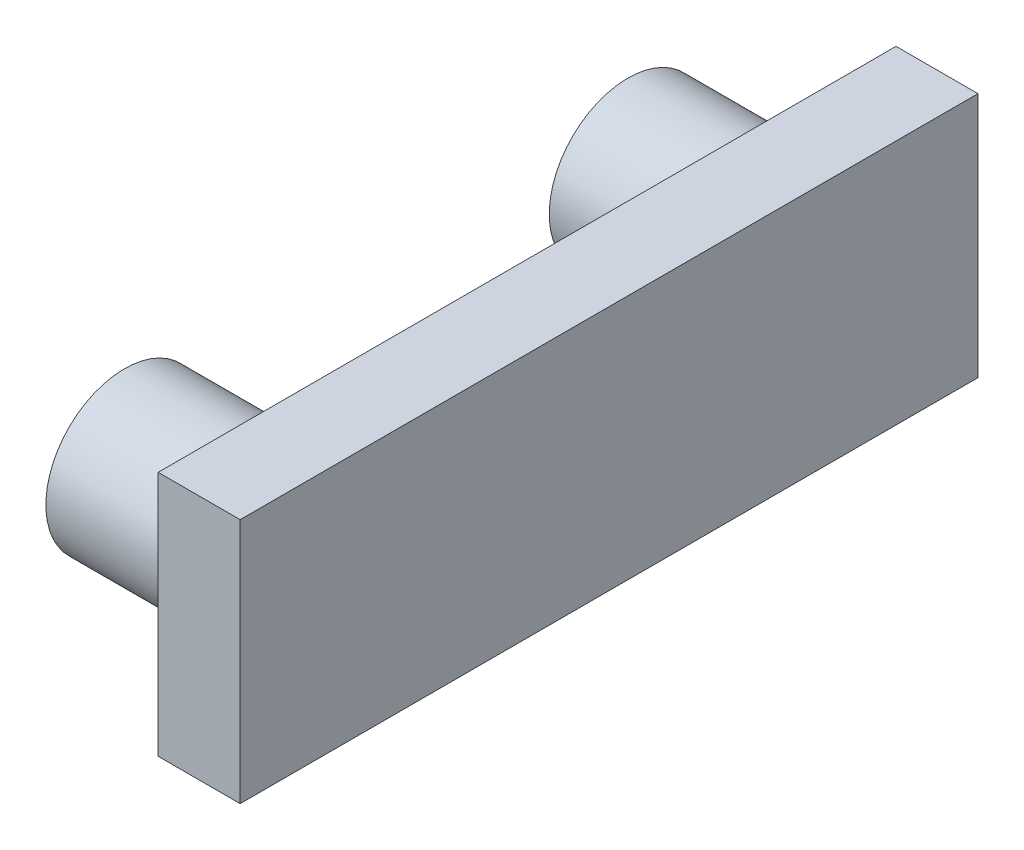
SolidWorks part; units mm, degrees
ref_plane "Front Plane" through (0, 0, 0) normal (1, 0, 0) x (0, 1, 0)
ref_plane "Top Plane" through (0, 0, 0) normal (0, 0, 1) x (0, 1, 0)
ref_plane "Right Plane" through (0, 0, 0) normal (0, 1, 0) x (-1, 0, 0)
sketch "Sketch1" plane through (0, 0, 0) normal (1, 0, 0) x (0, 1, 0)
  line L0 (-7.5, 0) -> (7.5, 0) construction
  line L1 (-7.5, 22.5) -> (7.5, 22.5)
  line L2 (-7.5, 22.5) -> (-7.5, -22.5)
  line L3 (-7.5, -22.5) -> (7.5, -22.5)
  line L4 (7.5, 22.5) -> (7.5, -22.5)
  line L5 (-7.5, 22.5) -> (7.5, -22.5) construction
  line L6 (-7.5, -22.5) -> (7.5, 22.5) construction
  circle A0 centre (0, 15.35) radius 4.8
  circle A1 centre (0, -15.35) radius 4.8
  point P0 (0, 0)
  point P10 (0, 0)
  point P13 (-0.7512, -10.35)
  point P14 (0, 0)
  dimension "D3" = 9.6
  dimension "D1" = 15
  dimension "D2" = 45
  dimension "D4" = 30.7
extrude "Boss-Extrude1" add sketch "Sketch1" along normal blind 5 contours A0 | A1 | L4 L1 L2 L3 A1 A0 region at (0, 0, 0) region at (0, 0, 15.35) region at (0, 0, -15.35)
extrude "Boss-Extrude2" add sketch "Sketch1<3>" against normal blind 9.2 contours A0 | A1
sketch "Sketch1<3>" plane through (0, 0, 0) normal (1, 0, 0) x (0, 1, 0) same geometry as "Sketch1"
